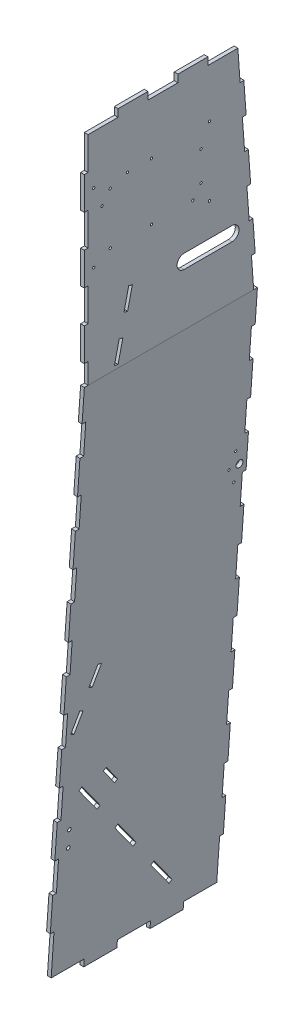
SolidWorks part; units mm, degrees
material "A-Glass Fiber"
ref_plane "Front Plane" through (0, 0, 0) normal (0, 0, 1) x (1, 0, 0)
ref_plane "Top Plane" through (0, 0, 0) normal (0, 1, 0) x (1, 0, 0)
ref_plane "Right Plane" through (0, 0, 0) normal (1, 0, 0) x (0, 0, -1)
sketch "Sketch1" plane through (0, 0, 0) normal (0, 0, 1) x (1, 0, 0)
  line L0 (-215.8818, 2052.32) -> (-215.8818, 1463.04)
  line L1 (-215.8818, 1463.04) -> (-316.0886, 20.32)
  line L2 (-316.0886, 20.32) -> (-317.5, 0)
  line L4 (-215.8818, 2052.32) -> (-215.8818, 2072.64)
  line L6 (-215.8818, 2072.64) -> (-205.7153, 2072.64)
  line L7 (-205.7153, 2072.64) -> (-205.7153, 1463.04)
  line L8 (-205.7153, 1463.04) -> (-307.3335, 0)
  line L9 (-317.5, 0) -> (-307.3335, 0)
  line L10 (-371.5407, 0) -> (-280.9748, 0) construction
  line L13 (-371.5407, 20.32) -> (-280.9748, 20.32) construction
  line L15 (-205.7153, 1463.04) -> (205.7153, 1463.04) construction
  point P23 (-305.9221, 20.32)
  dimension "D1" = 307.3335
extrude "Boss-Extrude1" add sketch "Sketch1" against normal blind 469.9
sketch "Sketch2" plane through (-315.9757, 21.9467, 0) normal (-0.9976, 0.0693, 0) x (0, 0, 1)
  line L35 (0, 1355.6785) -> (0, 0.1049)
  line L37 (-234.95, 1444.5652) -> (-234.95, -21.9996) construction
  line L40 (-10.16, 0.1049) -> (0, 0.1049)
  line L43 (-10.16, 0.1049) -> (-10.16, -21.9996)
  line L46 (0, 1272.0274) -> (-10.16, 1272.0274)
  line L47 (-10.16, 1355.6785) -> (-10.16, 1272.0274)
  line L48 (0, 1355.6785) -> (-10.16, 1355.6785)
  line L49 (0, 1177.9051) -> (-10.16, 1177.9051)
  line L50 (-10.16, 1177.9051) -> (-10.16, 1094.2274)
  line L51 (0, 1094.2274) -> (-10.16, 1094.2274)
  line L52 (0, 916.4274) -> (-10.16, 916.4274)
  line L53 (-10.16, 1000.1317) -> (-10.16, 916.4274)
  line L54 (0, 1000.1317) -> (-10.16, 1000.1317)
  line L55 (0, 822.3583) -> (-10.16, 822.3583)
  line L56 (0, 738.6274) -> (-10.16, 738.6274)
  line L57 (-10.16, 822.3583) -> (-10.16, 738.6274)
  line L58 (0, 644.5849) -> (-10.16, 644.5849)
  line L59 (-10.16, 644.5849) -> (-10.16, 560.8274)
  line L60 (0, 560.8274) -> (-10.16, 560.8274)
  line L61 (0, 466.8115) -> (-10.16, 466.8115)
  line L62 (-10.16, 466.8115) -> (-10.16, 383.0274)
  line L63 (0, 383.0274) -> (-10.16, 383.0274)
  line L64 (0, 289.0381) -> (-10.16, 289.0381)
  line L65 (-10.16, 289.0381) -> (-10.16, 205.2274)
  line L66 (0, 205.2274) -> (-10.16, 205.2274)
  line L67 (0, 111.2647) -> (-10.16, 111.2647)
  line L68 (-10.16, 111.2647) -> (-10.16, 0.1049)
  line L69 (0, 0.1049) -> (-10.16, 0.1049)
  line L70 (-10.16, -21.9996) -> (0, -21.9996)
  line L71 (0, 0.1049) -> (0, -21.9996)
  line L72 (-469.9, 1444.5652) -> (0, 1444.5652) construction
  line L73 (-469.9, -21.9996) -> (0, -21.9996) construction
  line L74 (-469.9, 0.1049) -> (-469.9, -21.9996)
  line L75 (-459.74, -21.9996) -> (-469.9, -21.9996)
  line L76 (-469.9, 0.1049) -> (-459.74, 0.1049)
  line L77 (-459.74, 111.2647) -> (-459.74, 0.1049)
  line L78 (-469.9, 111.2647) -> (-459.74, 111.2647)
  line L79 (-469.9, 205.2274) -> (-459.74, 205.2274)
  line L80 (-459.74, 289.0381) -> (-459.74, 205.2274)
  line L81 (-469.9, 289.0381) -> (-459.74, 289.0381)
  line L82 (-469.9, 383.0274) -> (-459.74, 383.0274)
  line L83 (-459.74, 466.8115) -> (-459.74, 383.0274)
  line L84 (-469.9, 466.8115) -> (-459.74, 466.8115)
  line L85 (-469.9, 560.8274) -> (-459.74, 560.8274)
  line L86 (-459.74, 644.5849) -> (-459.74, 560.8274)
  line L87 (-469.9, 644.5849) -> (-459.74, 644.5849)
  line L88 (-459.74, 822.3583) -> (-459.74, 738.6274)
  line L89 (-469.9, 738.6274) -> (-459.74, 738.6274)
  line L90 (-469.9, 822.3583) -> (-459.74, 822.3583)
  line L91 (-469.9, 1000.1317) -> (-459.74, 1000.1317)
  line L92 (-459.74, 1000.1317) -> (-459.74, 916.4274)
  line L93 (-469.9, 916.4274) -> (-459.74, 916.4274)
  line L94 (-469.9, 1094.2274) -> (-459.74, 1094.2274)
  line L95 (-459.74, 1177.9051) -> (-459.74, 1094.2274)
  line L96 (-469.9, 1177.9051) -> (-459.74, 1177.9051)
  line L97 (-469.9, 1355.6785) -> (-459.74, 1355.6785)
  line L98 (-459.74, 1355.6785) -> (-459.74, 1272.0274)
  line L99 (-469.9, 1272.0274) -> (-459.74, 1272.0274)
  line L100 (-459.74, 0.1049) -> (-459.74, -21.9996)
  line L101 (-459.74, 0.1049) -> (-469.9, 0.1049)
  line L102 (-469.9, 1355.6785) -> (-469.9, 0.1049)
  line L103 (-469.9, 1444.5652) -> (-469.9, -21.9996) construction
  line L104 (-459.74, 205.2274) -> (-469.9, 205.2274) construction
  line M1 (0, -21.9996) -> (0, 1444.5652)
  line M3 (-469.9, 1444.5652) -> (-469.9, -21.9996)
  line M4 (-469.9, -21.9996) -> (0, -21.9996)
extrude "Cut-Extrude1" cut sketch "Sketch2" against normal blind 10.16 contours L66 L35 L64 L65 | L69 L67 L68 M1 | L60 L35 L58 L59 | L63 L35 L61 L62 | L55 L57 L56 L35 | L35 L54 L53 L52 | L51 L35 L49 L50 | L35 L48 L47 L46 | L40 L43 M4 M1 | L100 L76 M3 M4 | L78 L76 L77 M3 | L81 L79 L80 M3 | L84 L82 L83 M3 | L87 L85 L86 M3 | L90 L89 L88 M3 | L93 L92 L91 M3 | L96 L94 L95 M3 | L99 L98 L97 M3 region at (-224.9388, 1332.6419, -464.82) region at (-237.2577, 1155.2825, -464.82) region at (-249.5765, 977.9231, -464.82) region at (-261.8953, 800.5637, -464.82) region at (-274.2142, 623.2043, -464.82) region at (-286.533, 445.8449, -464.82) region at (-298.8518, 268.4855, -464.82) region at (-316.7342, 11.0257, -464.82) region at (-312.1173, 77.4977, -5.08) region at (-298.8518, 268.4855, -5.08) region at (-286.533, 445.8449, -5.08) region at (-274.2142, 623.2043, -5.08) region at (-261.8953, 800.5637, -5.08) region at (-249.5765, 977.9231, -5.08) region at (-237.2577, 1155.2825, -5.08) region at (-224.9388, 1332.6419, -5.08) region at (-316.7342, 11.0257, -5.08) region at (-312.1173, 77.4977, -464.82)
sketch "Sketch3" plane through (-215.8818, 0, 0) normal (-1, 0, 0) x (0, 0, 1)
  line L0 (0, 2052.32) -> (-10.16, 2052.32) construction
  line L1 (0, 1963.42) -> (-10.16, 1963.42) construction
  line L2 (-10.16, 2052.32) -> (-10.16, 1963.42) construction
  line L3 (0, 1874.52) -> (-10.16, 1874.52) construction
  line L4 (0, 1463.04) -> (0, 2072.64)
  line L5 (0, 2072.64) -> (-469.9, 2072.64)
  line L6 (-469.9, 2072.64) -> (-469.9, 1463.04)
  line L8 (0, 1463.04) -> (0, 2072.64)
  line L9 (0, 2072.64) -> (-469.9, 2072.64)
  line L12 (0, 1785.62) -> (-10.16, 1785.62) construction
  line L13 (-10.16, 1874.52) -> (-10.16, 1785.62) construction
  line L14 (0, 1696.72) -> (-10.16, 1696.72) construction
  line L15 (0, 1607.82) -> (-10.16, 1607.82) construction
  line L16 (-10.16, 1696.72) -> (-10.16, 1607.82) construction
  line L17 (0, 1518.92) -> (-10.16, 1518.92) construction
  line L18 (-10.16, 1518.92) -> (-10.16, 1488.44) construction
  line L19 (0, 2052.32) -> (-10.16, 2052.32)
  line L20 (0, 1963.42) -> (-10.16, 1963.42)
  line L21 (-10.16, 2052.32) -> (-10.16, 1963.42)
  line L22 (0, 1874.52) -> (-10.16, 1874.52)
  line L23 (0, 1785.62) -> (-10.16, 1785.62)
  line L24 (-10.16, 1874.52) -> (-10.16, 1785.62)
  line L25 (0, 1696.72) -> (-10.16, 1696.72)
  line L26 (0, 1607.82) -> (-10.16, 1607.82)
  line L27 (-10.16, 1696.72) -> (-10.16, 1607.82)
  line L28 (0, 1518.92) -> (-10.16, 1518.92)
  line L29 (-10.16, 1518.92) -> (-10.16, 1488.44)
  line L30 (0, 2052.32) -> (0, 1463.04)
  line L31 (-234.95, 1463.04) -> (-234.95, 2072.64) construction
  line L32 (-10.16, 2052.32) -> (0, 2052.32)
  line L33 (-10.16, 2052.32) -> (-10.16, 2072.64)
  line L34 (-10.16, 2072.64) -> (0, 2072.64)
  line L35 (0, 2052.32) -> (0, 2072.64)
  line L36 (-469.9, 1463.04) -> (-425.45, 2072.64)
  line L37 (-469.9, 1463.04) -> (-463.754, 1547.3284)
  line L38 (-469.9, 1463.04) -> (-459.7669, 1462.3011)
  line L39 (-463.754, 1547.3284) -> (-453.6209, 1546.5895)
  line L40 (-459.7669, 1462.3011) -> (-453.6209, 1546.5895)
  line L41 (-463.754, 1547.3284) -> (-453.6209, 1546.5895)
  line L42 (-463.754, 1547.3284) -> (-457.6079, 1631.6168)
  line L43 (-453.6209, 1546.5895) -> (-447.4748, 1630.8779)
  line L44 (-457.6079, 1631.6168) -> (-447.4748, 1630.8779)
  line L45 (-457.6079, 1631.6168) -> (-447.4748, 1630.8779)
  line L46 (-457.6079, 1631.6168) -> (-451.4619, 1715.9052)
  line L47 (-447.4748, 1630.8779) -> (-441.3288, 1715.1664)
  line L48 (-451.4619, 1715.9052) -> (-441.3288, 1715.1664)
  line L49 (-451.4619, 1715.9052) -> (-441.3288, 1715.1664)
  line L50 (-451.4619, 1715.9052) -> (-445.3159, 1800.1936)
  line L51 (-441.3288, 1715.1664) -> (-435.1828, 1799.4548)
  line L52 (-445.3159, 1800.1936) -> (-435.1828, 1799.4548)
  line L53 (-445.3159, 1800.1936) -> (-435.1828, 1799.4548)
  line L54 (-10.16, 1488.44) -> (-10.16, 1463.04)
  line L56 (-445.3159, 1800.1936) -> (-439.1699, 1884.4821)
  line L57 (-435.1828, 1799.4548) -> (-429.0368, 1883.7432)
  line L58 (-439.1699, 1884.4821) -> (-429.0368, 1883.7432)
  line L59 (-439.1699, 1884.4821) -> (-429.0368, 1883.7432)
  line L60 (-439.1699, 1884.4821) -> (-433.0238, 1968.7705)
  line L61 (-429.0368, 1883.7432) -> (-422.8907, 1968.0316)
  line L62 (-433.0238, 1968.7705) -> (-422.8907, 1968.0316)
  line L63 (-10.16, 2052.32) -> (-469.9, 2052.32) construction
  line L64 (-469.9, 2072.64) -> (-469.9, 1463.04) construction
  line L65 (-433.0238, 1968.7705) -> (-422.8907, 1968.0316)
  line L66 (-433.0238, 1968.7705) -> (-426.8778, 2053.0589)
  line L67 (-422.8907, 1968.0316) -> (-416.7447, 2052.32)
  line L68 (-426.8778, 2053.0589) -> (-416.7447, 2052.32)
  line L69 (-416.7447, 2052.32) -> (-426.9317, 2052.32)
  line L70 (-426.8778, 2053.0589) -> (-416.7447, 2052.32)
  line L71 (-426.8778, 2053.0589) -> (-425.3531, 2073.9694)
  line L72 (-416.7447, 2052.32) -> (-415.22, 2073.2306)
  line L73 (-425.3531, 2073.9694) -> (-415.22, 2073.2306)
  line L74 (-469.9, 1463.04) -> (0, 1463.04) construction
  line L78 (-469.9, 1463.04) -> (0, 1463.04)
  line L79 (-469.9, 1463.04) -> (0, 1463.04)
  line M7 (0, 1463.04) -> (0, 2072.64)
  line M8 (0, 2072.64) -> (-469.9, 2072.64)
  line M9 (-469.9, 2072.64) -> (-469.9, 1463.04)
  line M10 (-469.9, 1463.04) -> (0, 1463.04)
  dimension "D2" = 44.45
  dimension "D3" = 10.16
  dimension "D1" = 0
extrude "Cut-Extrude2" cut sketch "Sketch3" against normal blind 12.7 contours M10 | L29 L54 L28 M10 M7 | L36 L66 M9 M8 | L48 L36 L44 L47 | L58 L36 L52 L57 | L67 L69 L36 L62 | L25 L27 L26 L8 | L22 L24 L23 L8 | L19 L21 L20 L8 | L33 L19 L8 M8 | L68 L72 L36 M8 | L69 L68 L66 region at (-215.8818, 1490.98, -5.08) region at (-215.8818, 1652.27, -5.08) region at (-215.8818, 1504.9998, -461.7544) region at (-215.8818, 1869.44, -455.0833) region at (-215.8818, 1830.07, -5.08) region at (-215.8818, 1673.3916, -449.4684) region at (-215.8818, 2062.6636, -421.0525) region at (-215.8818, 2007.87, -5.08) region at (-215.8818, 1841.9684, -437.1763) region at (-215.8818, 2052.5663, -423.5181) region at (-215.8818, 2062.48, -5.08) region at (-215.8818, 2010.3602, -424.8903)
sketch "Sketch4" plane through (-215.8818, 0, 0) normal (-1, 0, 0) x (0, 0, 1)
  line L1 (-416.7447, 2072.64) -> (-335.4278, 2072.64)
  line L2 (-416.7447, 2072.64) -> (-416.7447, 2052.32)
  line L3 (-416.7447, 2052.32) -> (-335.4278, 2052.32)
  line L4 (-335.4278, 2072.64) -> (-335.4278, 2052.32)
  line L5 (-10.16, 2072.64) -> (-10.16, 1963.42) construction
  line L6 (-335.4278, 2072.64) -> (-254.1108, 2072.64)
  line L7 (-335.4278, 2072.64) -> (-335.4278, 2052.32)
  line L8 (-335.4278, 2052.32) -> (-254.1108, 2052.32)
  line L9 (-254.1108, 2072.64) -> (-254.1108, 2052.32)
  line L10 (-254.1108, 2072.64) -> (-172.7939, 2072.64)
  line L11 (-254.1108, 2072.64) -> (-254.1108, 2052.32)
  line L12 (-254.1108, 2052.32) -> (-172.7939, 2052.32)
  line L13 (-172.7939, 2072.64) -> (-172.7939, 2052.32)
  line L14 (-172.7939, 2072.64) -> (-91.4769, 2072.64)
  line L15 (-172.7939, 2072.64) -> (-172.7939, 2052.32)
  line L16 (-172.7939, 2052.32) -> (-91.4769, 2052.32)
  line L17 (-91.4769, 2072.64) -> (-91.4769, 2052.32)
  line L18 (-91.4769, 2072.64) -> (-10.16, 2072.64)
  line L19 (-91.4769, 2072.64) -> (-91.4769, 2052.32)
  line L20 (-91.4769, 2052.32) -> (-10.16, 2052.32)
  line L21 (-10.16, 2072.64) -> (-10.16, 2052.32)
  line L23 (-422.8907, 1968.0316) -> (-415.263, 2072.64) construction
  line L24 (-415.263, 2072.64) -> (-10.16, 2072.64) construction
  line M26 (-10.16, 1963.42) -> (-10.16, 2072.64)
  line M27 (-10.16, 2072.64) -> (-415.263, 2072.64)
  dimension "D1" = 20.32
extrude "Cut-Extrude3" cut sketch "Sketch4" against normal blind 12.7 contours L4 L3 M27 | L13 L9 L12 M27 | L17 L20 M26 M27 region at (-215.8818, 2062.48, -376.0862) region at (-215.8818, 2062.48, -213.4523) region at (-215.8818, 2062.48, -50.8185)
sketch "Sketch5" plane through (-315.9757, 21.9467, 0) normal (-0.9976, 0.0693, 0) x (0, 0, 1)
  line L1 (-459.74, -21.9996) -> (-369.824, -21.9996)
  line L2 (-459.74, -21.9996) -> (-459.74, -1.6796)
  line L3 (-459.74, -1.6796) -> (-369.824, -1.6796)
  line L4 (-369.824, -21.9996) -> (-369.824, -1.6796)
  line L5 (-369.824, -21.9996) -> (-279.908, -21.9996)
  line L6 (-369.824, -21.9996) -> (-369.824, -1.6796)
  line L7 (-369.824, -1.6796) -> (-279.908, -1.6796)
  line L8 (-279.908, -21.9996) -> (-279.908, -1.6796)
  line L9 (-279.908, -21.9996) -> (-189.992, -21.9996)
  line L10 (-279.908, -21.9996) -> (-279.908, -1.6796)
  line L11 (-279.908, -1.6796) -> (-189.992, -1.6796)
  line L12 (-189.992, -21.9996) -> (-189.992, -1.6796)
  line L13 (-189.992, -21.9996) -> (-100.076, -21.9996)
  line L14 (-189.992, -21.9996) -> (-189.992, -1.6796)
  line L15 (-189.992, -1.6796) -> (-100.076, -1.6796)
  line L16 (-100.076, -21.9996) -> (-100.076, -1.6796)
  line L17 (-100.076, -21.9996) -> (-10.16, -21.9996)
  line L18 (-100.076, -21.9996) -> (-100.076, -1.6796)
  line L19 (-100.076, -1.6796) -> (-10.16, -1.6796)
  line L20 (-10.16, -21.9996) -> (-10.16, -1.6796)
  line L21 (-10.16, 111.2647) -> (-10.16, -21.9996) construction
  dimension "D1" = 20.32
extrude "Cut-Extrude4" cut sketch "Sketch5" against normal blind 12.7 contours L1 L4 L3 L2 | L9 L12 L11 L8 | L17 L20 L19 L18 L16 region at (-316.796, 10.1356, -414.782) region at (-316.796, 10.1356, -234.95) region at (-316.796, 10.1356, -55.118)
sketch "Sketch6" plane through (-315.9757, 21.9467, 0) normal (-0.9976, 0.0693, 0) x (0, 0, 1)
  line L0 (-217.3726, 211.9965) -> (-163.4402, 285.2141)
  line L1 (-325.2304, 65.5562) -> (-271.298, 138.7738)
  line L2 (-44.1085, 632.6765) -> (-22.5289, 586.4358) construction
  line L3 (-74.8989, 674.6188) -> (-65.6881, 678.9173) construction
  line L8 (-271.6486, 139.032) -> (-279.8219, 145.0526) construction
  line L56 (-87.2678, 725.158) -> (-65.6881, 678.9173) construction
  line L57 (-74.8989, 674.6188) -> (-96.4785, 720.8595) construction
  line L58 (-31.7396, 582.1373) -> (-22.5289, 586.4358) construction
  line L59 (-31.7396, 582.1373) -> (-53.3192, 628.3781) construction
  line L60 (-53.3192, 628.3781) -> (-44.1085, 632.6765) construction
  line L63 (-117.6881, 364.4573) -> (-63.7557, 437.6749) construction
  line L65 (-225.5528, 218.0222) -> (-171.6205, 291.2397) construction
  line L69 (-333.4176, 71.587) -> (-279.4852, 144.8046) construction
  line L70 (-109.5008, 358.4266) -> (-55.5685, 431.6442)
  line L71 (-44.1085, 632.6765) -> (-22.5289, 586.4358)
  line L72 (-74.8989, 674.6188) -> (-65.6881, 678.9173)
  line L73 (-87.2678, 725.158) -> (-65.6881, 678.9173)
  line L74 (-74.8989, 674.6188) -> (-96.4785, 720.8595)
  line L75 (-31.7396, 582.1373) -> (-22.5289, 586.4358)
  line L76 (-31.7396, 582.1373) -> (-53.3192, 628.3781)
  line L77 (-53.3192, 628.3781) -> (-44.1085, 632.6765)
  line L78 (-109.5008, 358.4266) -> (-117.6881, 364.4573)
  line L79 (-55.5685, 431.6442) -> (-63.7557, 437.6749)
  line L80 (-117.6881, 364.4573) -> (-63.7557, 437.6749)
  line L81 (-163.4402, 285.2141) -> (-171.6205, 291.2397)
  line L82 (-225.5528, 218.0222) -> (-171.6205, 291.2397)
  line L83 (-217.3726, 211.9965) -> (-225.5528, 218.0222)
  line L84 (-271.298, 138.7738) -> (-279.4852, 144.8046)
  line L85 (-325.2304, 65.5562) -> (-333.4176, 71.587)
  line L86 (-333.4176, 71.587) -> (-279.4852, 144.8046)
  line L87 (-87.2678, 725.158) -> (-96.4785, 720.8595)
  line L89 (-109.8514, 358.6848) -> (-118.0248, 364.7053) construction
  line L90 (-163.7838, 285.4672) -> (-171.9572, 291.4877) construction
  line L91 (-217.7162, 212.2496) -> (-225.8895, 218.2702) construction
  dimension "D1" = 10.16
extrude "Cut-Extrude5" cut sketch "Sketch6" against normal blind 137.414 contours L73 L87 L74 L72 | L77 L76 L75 L71 | L80 L78 | L83 L81 L82 | L86 L85 L84 region at (-298.541, 272.9601, -194.4965) region at (-308.6877, 126.8743, -302.3578) region at (-288.3947, 419.0407, -86.6283) region at (-273.8885, 627.8938, -37.9241) region at (-267.4804, 720.1529, -81.0833)
sketch "Sketch8" plane through (-215.8818, 0, 0) normal (-1, 0, 0) x (0, 0, 1)
  circle A0 centre (-450.215, 1043.94) radius 9.525 construction
  circle A1 centre (-450.215, 1043.94) radius 9.525
extrude "Cut-Extrude7" cut sketch "Sketch8" along normal through all
sketch "Sketch13" plane through (-215.8818, 0, 0) normal (-1, 0, 0) x (0, 0, 1)
  line L0 (-413.556, 1633.6344) -> (-413.556, 1614.5844)
  line L1 (-270.8715, 1611.4094) -> (-270.8715, 1636.8094)
  line L2 (-413.556, 1624.1094) -> (-270.8715, 1624.1094) construction
  line L3 (-270.8715, 1624.1094) -> (-400.856, 1624.1094) construction
  line L4 (-270.8715, 1605.0594) -> (-400.856, 1605.0594)
  line L5 (-270.8715, 1643.1594) -> (-400.856, 1643.1594)
  line L6 (-416.7447, 2052.32) -> (-335.4278, 2052.32)
  line L7 (-422.8907, 1968.0316) -> (-416.7447, 2052.32)
  circle A0 centre (-25.2465, 1731.87) radius 3.175
  circle A1 centre (-70.409, 1755.42) radius 3.175
  circle A2 centre (-182.409, 1755.42) radius 3.175
  circle A3 centre (-25.2465, 1918.97) radius 3.175
  circle A4 centre (-47.789, 1865.42) radius 3.175
  circle A5 centre (-182.409, 1910.42) radius 3.175
  circle A6 centre (-117.079, 1910.42) radius 3.175
  circle A7 centre (-70.409, 1895.42) radius 3.175
  circle A8 centre (-317.029, 1865.42) radius 3.175
  circle A9 centre (-294.409, 1755.42) radius 3.175
  circle A10 centre (-317.029, 1785.42) radius 3.175
  circle A11 centre (-339.5715, 1731.87) radius 3.175
  circle A12 centre (-339.5715, 1918.97) radius 3.175
  arc A13 (-270.8715, 1605.0594) -> (-270.8715, 1643.1594) centre (-270.8715, 1624.1094) ccw
  arc A14 (-400.856, 1643.1594) -> (-400.856, 1605.0594) centre (-400.856, 1624.1094) ccw
  point P34 (-335.8637, 1624.1094)
  point P42 (-416.7447, 2052.32)
  dimension "D1" = 12.7
  dimension "D2" = 19.05
extrude "Cut-Extrude8" cut sketch "Sketch13" against normal through all contours L5 A14 L4 A13 | A11 | A10 | A9 | A2 | A1 | A0 | A4 | A7 | A6 | A3 | A5 | A8 | A12 | L0 A14 region at (-215.8818, 1624.1094, -335.8637) region at (-215.8818, 1731.87, -25.2465) region at (-215.8818, 1755.42, -70.409) region at (-215.8818, 1755.42, -182.409) region at (-215.8818, 1918.97, -25.2465) region at (-215.8818, 1865.42, -47.789) region at (-215.8818, 1910.42, -182.409) region at (-215.8818, 1910.42, -117.079) region at (-215.8818, 1895.42, -70.409) region at (-215.8818, 1865.42, -317.029) region at (-215.8818, 1755.42, -294.409) region at (-215.8818, 1785.42, -317.029) region at (-215.8818, 1731.87, -339.5715) region at (-215.8818, 1918.97, -339.5715)
sketch "Sketch17" plane through (-215.8818, 0, 0) normal (-1, 0, 0) x (0, 0, 1)
  line L0 (-130.4243, 1639.6605) -> (-120.5247, 1641.946)
  line L1 (-120.5247, 1641.946) -> (-107.584, 1585.8939)
  line L2 (-130.4243, 1639.6605) -> (-117.4836, 1583.6084)
  line L3 (-117.4836, 1583.6084) -> (-107.584, 1585.8939)
  line L4 (-104.543, 1527.5563) -> (-94.6434, 1529.8418)
  line L5 (-91.6023, 1471.5043) -> (-104.543, 1527.5563)
  line L6 (-91.6023, 1471.5043) -> (-81.7027, 1473.7898)
  line L7 (-81.7027, 1473.7898) -> (-94.6434, 1529.8418)
  line L8 (-416.7447, 2052.32) -> (-335.4278, 2052.32)
  line L9 (-422.8907, 1968.0316) -> (-416.7447, 2052.32)
  line L10 (-96.4785, 740.3709) -> (-87.2678, 744.6591) construction
  line L11 (-65.6881, 698.5295) -> (-74.8989, 694.2413) construction
  line L12 (-96.4785, 740.3709) -> (-74.8989, 694.2413) construction
  line L13 (-65.6881, 698.5295) -> (-87.2678, 744.6591) construction
  line L14 (-96.4785, 740.3709) -> (-87.2678, 744.6591)
  line L15 (-65.6881, 698.5295) -> (-74.8989, 694.2413)
  line L16 (-96.4785, 740.3709) -> (-74.8989, 694.2413)
  line L17 (-65.6881, 698.5295) -> (-87.2678, 744.6591)
  line L18 (-87.2678, 744.6591) -> (-87.2678, 1303.4591)
  line L84 (-369.824, 19.5684) -> (-369.824, 0)
  line L85 (-459.74, 19.5684) -> (-369.824, 19.5684)
  line L86 (-459.74, 132.2412) -> (-459.74, 19.5684)
  line L87 (-469.9, 132.2412) -> (-459.74, 132.2412)
  line L88 (-469.9, 225.9781) -> (-469.9, 132.2412)
  line L89 (-459.74, 225.9781) -> (-469.9, 225.9781)
  line L90 (-459.74, 309.5874) -> (-459.74, 225.9781)
  line L91 (-469.9, 309.5874) -> (-459.74, 309.5874)
  line L92 (-469.9, 403.3508) -> (-469.9, 309.5874)
  line L93 (-459.74, 403.3508) -> (-469.9, 403.3508)
  line L94 (-459.74, 486.9335) -> (-459.74, 403.3508)
  line L95 (-469.9, 486.9335) -> (-459.74, 486.9335)
  line L96 (-469.9, 580.7234) -> (-469.9, 486.9335)
  line L97 (-459.74, 580.7234) -> (-469.9, 580.7234)
  line L98 (-459.74, 664.2796) -> (-459.74, 580.7234)
  line L99 (-469.9, 664.2796) -> (-459.74, 664.2796)
  line L100 (-469.9, 758.0961) -> (-469.9, 664.2796)
  line L101 (-459.74, 758.0961) -> (-469.9, 758.0961)
  line L102 (-459.74, 841.6258) -> (-459.74, 758.0961)
  line L103 (-469.9, 841.6258) -> (-459.74, 841.6258)
  line L104 (-469.9, 935.4688) -> (-469.9, 841.6258)
  line L105 (-459.74, 935.4688) -> (-469.9, 935.4688)
  line L106 (-459.74, 1018.9719) -> (-459.74, 935.4688)
  line L107 (-469.9, 1018.9719) -> (-459.74, 1018.9719)
  line L108 (-469.9, 1112.8414) -> (-469.9, 1018.9719)
  line L109 (-459.74, 1112.8414) -> (-469.9, 1112.8414)
  line L110 (-459.74, 1196.3181) -> (-459.74, 1112.8414)
  line L111 (-469.9, 1196.3181) -> (-459.74, 1196.3181)
  line L112 (-469.9, 1290.2141) -> (-469.9, 1196.3181)
  line L113 (-459.74, 1290.2141) -> (-469.9, 1290.2141)
  line L114 (-459.74, 1373.6642) -> (-459.74, 1290.2141)
  line L115 (-469.9, 1373.6642) -> (-459.74, 1373.6642)
  line L116 (-469.9, 1463.04) -> (-469.9, 1373.6642)
  line L117 (-459.713, 1463.04) -> (-469.9, 1463.04)
  line L118 (-10.16, 1463.04) -> (-459.713, 1463.04)
  line L119 (0, 1463.04) -> (-10.16, 1463.04)
  line L120 (0, 1373.6642) -> (0, 1463.04)
  line L121 (-10.16, 1373.6642) -> (0, 1373.6642)
  line L122 (-10.16, 1290.2141) -> (-10.16, 1373.6642)
  line L123 (0, 1290.2141) -> (-10.16, 1290.2141)
  line L124 (0, 1196.3181) -> (0, 1290.2141)
  line L125 (-10.16, 1196.3181) -> (0, 1196.3181)
  line L126 (-10.16, 1112.8414) -> (-10.16, 1196.3181)
  line L127 (0, 1112.8414) -> (-10.16, 1112.8414)
  line L128 (0, 1018.9719) -> (0, 1112.8414)
  line L129 (-10.16, 1018.9719) -> (0, 1018.9719)
  line L130 (-10.16, 935.4688) -> (-10.16, 1018.9719)
  line L131 (0, 935.4688) -> (-10.16, 935.4688)
  line L132 (0, 841.6258) -> (0, 935.4688)
  line L133 (-10.16, 841.6258) -> (0, 841.6258)
  line L134 (-10.16, 758.0961) -> (-10.16, 841.6258)
  line L135 (0, 758.0961) -> (-10.16, 758.0961)
  line L136 (0, 664.2796) -> (0, 758.0961)
  line L137 (-10.16, 664.2796) -> (0, 664.2796)
  line L138 (-10.16, 580.7234) -> (-10.16, 664.2796)
  line L139 (0, 580.7234) -> (-10.16, 580.7234)
  line L140 (0, 486.9335) -> (0, 580.7234)
  line L141 (-10.16, 486.9335) -> (0, 486.9335)
  line L142 (-10.16, 403.3508) -> (-10.16, 486.9335)
  line L143 (0, 403.3508) -> (-10.16, 403.3508)
  line L144 (0, 309.5874) -> (0, 403.3508)
  line L145 (-10.16, 309.5874) -> (0, 309.5874)
  line L146 (-10.16, 225.9781) -> (-10.16, 309.5874)
  line L147 (0, 225.9781) -> (-10.16, 225.9781)
  line L148 (0, 132.2412) -> (0, 225.9781)
  line L149 (-10.16, 132.2412) -> (0, 132.2412)
  line L150 (-10.16, 19.5684) -> (-10.16, 132.2412)
  line L151 (-100.076, 19.5684) -> (-10.16, 19.5684)
  line L152 (-100.076, 0) -> (-100.076, 19.5684)
  line L153 (-189.992, 0) -> (-100.076, 0)
  line L154 (-189.992, 19.5684) -> (-189.992, 0)
  line L155 (-279.908, 19.5684) -> (-189.992, 19.5684)
  line L156 (-279.908, 0) -> (-279.908, 19.5684)
  line L157 (-369.824, 0) -> (-279.908, 0)
  line L158 (-369.824, 19.5684) -> (-369.824, 0)
  line L159 (-459.74, 19.5684) -> (-369.824, 19.5684)
  line L160 (-459.74, 132.2412) -> (-459.74, 19.5684)
  line L161 (-469.9, 132.2412) -> (-459.74, 132.2412)
  line L162 (-469.9, 225.9781) -> (-469.9, 132.2412)
  line L163 (-459.74, 225.9781) -> (-469.9, 225.9781)
  line L164 (-459.74, 309.5874) -> (-459.74, 225.9781)
  line L165 (-469.9, 309.5874) -> (-459.74, 309.5874)
  line L166 (-469.9, 403.3508) -> (-469.9, 309.5874)
  line L167 (-459.74, 403.3508) -> (-469.9, 403.3508)
  line L168 (-459.74, 486.9335) -> (-459.74, 403.3508)
  line L169 (-469.9, 486.9335) -> (-459.74, 486.9335)
  line L170 (-469.9, 580.7234) -> (-469.9, 486.9335)
  line L171 (-459.74, 580.7234) -> (-469.9, 580.7234)
  line L172 (-459.74, 664.2796) -> (-459.74, 580.7234)
  line L173 (-469.9, 664.2796) -> (-459.74, 664.2796)
  line L174 (-469.9, 758.0961) -> (-469.9, 664.2796)
  line L175 (-459.74, 758.0961) -> (-469.9, 758.0961)
  line L176 (-459.74, 841.6258) -> (-459.74, 758.0961)
  line L177 (-469.9, 841.6258) -> (-459.74, 841.6258)
  line L178 (-469.9, 935.4688) -> (-469.9, 841.6258)
  line L179 (-459.74, 935.4688) -> (-469.9, 935.4688)
  line L180 (-459.74, 1018.9719) -> (-459.74, 935.4688)
  line L181 (-469.9, 1018.9719) -> (-459.74, 1018.9719)
  line L182 (-469.9, 1112.8414) -> (-469.9, 1018.9719)
  line L183 (-459.74, 1112.8414) -> (-469.9, 1112.8414)
  line L184 (-459.74, 1196.3181) -> (-459.74, 1112.8414)
  line L185 (-469.9, 1196.3181) -> (-459.74, 1196.3181)
  line L186 (-469.9, 1290.2141) -> (-469.9, 1196.3181)
  line L187 (-459.74, 1290.2141) -> (-469.9, 1290.2141)
  line L188 (-459.74, 1373.6642) -> (-459.74, 1290.2141)
  line L189 (-469.9, 1373.6642) -> (-459.74, 1373.6642)
  line L190 (-469.9, 1463.04) -> (-469.9, 1373.6642)
  line L191 (-459.713, 1463.04) -> (-469.9, 1463.04)
  line L192 (-10.16, 1463.04) -> (-459.713, 1463.04)
  line L193 (0, 1463.04) -> (-10.16, 1463.04)
  line L194 (0, 1373.6642) -> (0, 1463.04)
  line L195 (-10.16, 1373.6642) -> (0, 1373.6642)
  line L196 (-10.16, 1290.2141) -> (-10.16, 1373.6642)
  line L197 (0, 1290.2141) -> (-10.16, 1290.2141)
  line L198 (0, 1196.3181) -> (0, 1290.2141)
  line L199 (-10.16, 1196.3181) -> (0, 1196.3181)
  line L200 (-10.16, 1112.8414) -> (-10.16, 1196.3181)
  line L201 (0, 1112.8414) -> (-10.16, 1112.8414)
  line L202 (0, 1018.9719) -> (0, 1112.8414)
  line L203 (-10.16, 1018.9719) -> (0, 1018.9719)
  line L204 (-10.16, 935.4688) -> (-10.16, 1018.9719)
  line L205 (0, 935.4688) -> (-10.16, 935.4688)
  line L206 (0, 841.6258) -> (0, 935.4688)
  line L207 (-10.16, 841.6258) -> (0, 841.6258)
  line L208 (-10.16, 758.0961) -> (-10.16, 841.6258)
  line L209 (0, 758.0961) -> (-10.16, 758.0961)
  line L210 (0, 664.2796) -> (0, 758.0961)
  line L211 (-10.16, 664.2796) -> (0, 664.2796)
  line L212 (-10.16, 580.7234) -> (-10.16, 664.2796)
  line L213 (0, 580.7234) -> (-10.16, 580.7234)
  line L214 (0, 486.9335) -> (0, 580.7234)
  line L215 (-10.16, 486.9335) -> (0, 486.9335)
  line L216 (-10.16, 403.3508) -> (-10.16, 486.9335)
  line L217 (0, 403.3508) -> (-10.16, 403.3508)
  line L218 (0, 309.5874) -> (0, 403.3508)
  line L219 (-10.16, 309.5874) -> (0, 309.5874)
  line L220 (-10.16, 225.9781) -> (-10.16, 309.5874)
  line L221 (0, 225.9781) -> (-10.16, 225.9781)
  line L222 (0, 132.2412) -> (0, 225.9781)
  line L223 (-10.16, 132.2412) -> (0, 132.2412)
  line L224 (-10.16, 19.5684) -> (-10.16, 132.2412)
  line L225 (-100.076, 19.5684) -> (-10.16, 19.5684)
  line L226 (-100.076, 0) -> (-100.076, 19.5684)
  line L227 (-189.992, 0) -> (-100.076, 0)
  line L228 (-189.992, 19.5684) -> (-189.992, 0)
  line L229 (-279.908, 19.5684) -> (-189.992, 19.5684)
  line L230 (-279.908, 0) -> (-279.908, 19.5684)
  line L231 (-369.824, 0) -> (-279.908, 0)
  point P11 (-416.7447, 2052.32)
  dimension "D2" = 558.8
  dimension "D1" = 0
extrude "Cut-Extrude9" cut sketch "Sketch17" against normal through all contours L6 L7 L4 L5 | L2 L3 L1 L0 region at (-215.8818, 1612.7772, -119.0041) region at (-215.8818, 1500.6731, -93.1229)
sketch "Sketch20" plane through (-315.9757, 21.9467, 0) normal (-0.9976, 0.0693, 0) x (0, 0, 1)
  line L0 (-441.6805, 375.8656) -> (-258.1103, 563.7707)
  line L1 (-258.1103, 563.7707) -> (-341.7803, 797.9819)
  line L2 (-258.1103, 563.7707) -> (-10.16, 315.8204)
  line L3 (-258.1103, 563.7707) -> (-258.6478, 797.9819)
  line L8 (-10.16, 110.1771) -> (-10.16, -1.6796)
  line L9 (-10.16, 466.8115) -> (-10.16, 383.0274) construction
  line L10 (-13.335, 290.1376) -> (-13.335, 359.9876)
  line L11 (-13.335, 290.1376) -> (-48.26, 290.1376)
  line L12 (-13.335, 359.9876) -> (-48.26, 359.9876)
  line L13 (-48.26, 290.1376) -> (-48.26, 359.9876)
  line L32 (-120.9293, 445.7124) -> (-154.8235, 399.6982)
  line L33 (-120.9293, 445.7124) -> (-128.5983, 451.3614)
  line L34 (-154.8235, 399.6982) -> (-162.4926, 405.3473)
  line L35 (-128.5983, 451.3614) -> (-162.4926, 405.3473)
  line L37 (-109.5008, 358.4266) -> (-117.6881, 364.4573) construction
  line L38 (-117.6881, 364.4573) -> (-63.7557, 437.6749) construction
  line L39 (-137.8764, 422.7053) -> (43.6586, 288.9858) construction
  line L40 (-35.56, 332.8883) -> (-35.56, 361.687) construction
  line L41 (-10.16, 466.8115) -> (-10.16, 383.0274)
  circle A0 centre (-35.56, 347.2876) radius 4.7625
  circle A2 centre (-35.56, 302.8376) radius 4.7625
  point P11 (-10.16, -1.6796)
  point P57 (-35.56, 341.2204)
  dimension "D9" = 44.45
  dimension "D15" = 9.525
  dimension "D3" = 3.175
  dimension "D4" = 12.7
  dimension "D5" = 57.15
  dimension "D6" = 317.5
  dimension "D7" = 12.7
  dimension "D8" = 12.7
  dimension "D22" = 9.525
  dimension "D23" = 6.35
  dimension "D24" = 50.8
  dimension "D25" = 34.925
extrude "Cut-Extrude10" cut sketch "Sketch20" against normal through all contours A2 | L2 A0 | L2 A0 | L2 L35 L34 L32 | L33 L35 L2 L32 region at (-285.2619, 464.1454, -128.5379) region at (-286.8509, 441.2683, -145.572) region at (-291.908, 368.4591, -35.5004) region at (-292.1316, 365.2395, -38.7278) region at (-294.992, 324.0565, -35.56)
sketch "Sketch22" [suppressed] plane through (-315.9757, 21.9467, 0) normal (-0.9976, 0.0693, 0) x (0, 0, 1)
  line L3 (-138.6114, 421.183) -> (-138.6114, 431.343)
  line L4 (-138.6114, 431.343) -> (-202.8371, 431.343)
  line L5 (-138.6114, 421.183) -> (-202.8371, 421.183)
  line L6 (-202.8371, 421.183) -> (-202.8371, 431.343)
  line L7 (-267.0629, 421.183) -> (-267.0629, 431.343)
  line L8 (-267.0629, 431.343) -> (-331.2886, 431.343)
  line L9 (-267.0629, 421.183) -> (-331.2886, 421.183)
  line L10 (-331.2886, 421.183) -> (-331.2886, 431.343)
  line L11 (-395.5143, 421.183) -> (-395.5143, 431.343)
  line L12 (-395.5143, 421.183) -> (-459.74, 421.183)
  line L13 (-395.5143, 431.343) -> (-459.74, 431.343)
  line L15 (-459.74, 421.183) -> (-459.74, 431.343)
  line L16 (-100.076, -1.6796) -> (-10.16, -1.6796) construction
  line L17 (-10.16, 111.2647) -> (-10.16, -1.6796) construction
  line L18 (-100.076, -1.6796) -> (-10.16, -1.6796)
  line L19 (-10.16, 111.2647) -> (-10.16, -1.6796)
  point P0 (-10.16, -1.6796)
sketch "Sketch23" plane through (-315.9757, 21.9467, 0) normal (-0.9976, 0.0693, 0) x (0, 0, 1)
  line L2 (-450.215, 1024.4555) -> (-396.5689, 1024.4555) construction
  line L3 (-437.515, 986.3555) -> (-437.515, 1062.5555) construction
  circle A0 centre (-437.515, 986.3555) radius 3.175
  circle A1 centre (-421.64, 1024.4555) radius 3.175
  circle A2 centre (-437.515, 1062.5555) radius 3.175
  point P21 (-437.515, 1024.4555)
  dimension "D1" = 6.35
  dimension "D2" = 28.575
  dimension "D3" = 76.2
  dimension "D4" = 12.7
extrude "Cut-Extrude11" cut sketch "Sketch23" against normal through all contours A1 | A0 | A2 region at (-247.6311, 1005.9316, -437.515) region at (-244.9912, 1043.94, -421.64) region at (-242.3512, 1081.9484, -437.515)
